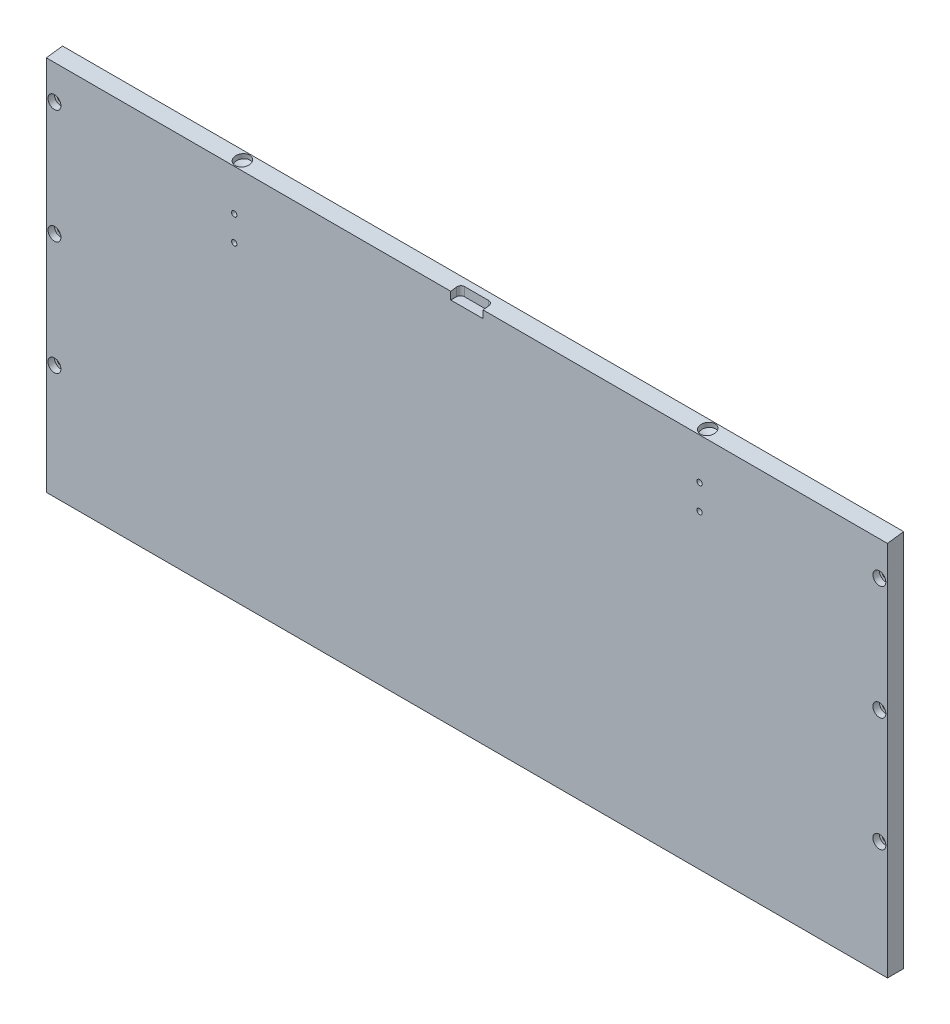
SolidWorks part; units mm, degrees
material "Bakelite Black"
ref_plane "Front" through (0, 0, 0) normal (0, 0, 1) x (1, 0, 0)
ref_plane "Top" through (0, 0, 0) normal (0, 1, 0) x (1, 0, 0)
ref_plane "Right" through (0, 0, 0) normal (1, 0, 0) x (0, 0, -1)
sketch "Sketch1" plane through (0, 0, 0) normal (0, 0, 1) x (1, 0, 0)
  line L1 (0, 0) -> (520, 0)
  line L2 (0, 0) -> (0, 234)
  line L3 (0, 234) -> (520, 234)
  line L4 (520, 0) -> (520, 234)
  dimension "D1" = 234
  dimension "D2" = 520
extrude "Boss-Extrude1" add sketch "Sketch1" along normal blind 10
ref_plane "Plane1" through (260, 0, 0) normal (-1, 0, 0) x (0, 0, 1)
sketch "Sketch8" plane through (0, 0, 10) normal (0, 0, 1) x (1, 0, 0)
  line L0 (260, 5.5) -> (260, -5.5) construction
  line L1 (250, 228) -> (270, 228)
  line L2 (250, 228) -> (250, 236)
  line L3 (250, 236) -> (270, 236)
  line L4 (270, 228) -> (270, 236)
  line L5 (250, 228) -> (270, 236) construction
  line L6 (250, 236) -> (270, 228) construction
  line L7 (520, 234) -> (0, 234) construction
  point P0 (260, 232)
  dimension "D1" = 20
  dimension "D2" = 8
  dimension "D3" = 6
extrude "Cut-Extrude5" cut sketch "Sketch8" against normal blind 6
fillet "Fillet2" radius 2.5 2 edges at (270, 231, 4) (250, 231, 4)
sketch "Sketch9" plane through (0, 0, 0) normal (1, 0, 0) x (0, 0, -1)
  line L0 (0, 234) -> (-10, 232.6853)
  line L1 (-10, 234) -> (-10, 0) construction
  line L2 (-10, 232.6853) -> (-10, 234)
  line L3 (-10, 234) -> (0, 234)
  dimension "D1" = 7.49
extrude "Cut-Extrude7" cut sketch "Sketch9" along normal through all
hole_wizard "M4x0.7 Tapped Hole1" positions "Sketch10" profile "Sketch11" tap size "M4x0.7" standard "ANSI Metric"
sketch "Sketch10" plane through (0, 0, 0) normal (0, -1, 0) x (-1, 0, 0)
  line L0 (-260, -8.8296) -> (-260, 8.8296) construction
  line L1 (0, 0) -> (-520, 0) construction
  point P0 (-70, -5)
  point P2 (-260, -5)
  point P4 (-450, -5)
  dimension "D1" = 190
  dimension "D2" = 190
  dimension "D3" = 5
sketch "Sketch11" plane through (70, 0, 5) normal (1, 0, 0) x (0, 0, -1)
  line L0 (0, 0) -> (0, 12.9914)
  line L1 (0, 12.9914) -> (1.65, 12)
  line L2 (1.65, 12) -> (1.65, 0)
  line L5 (1.65, 0) -> (0, 0)
  line L10 (0, 12.9914) -> (-1.65, 12) construction
  line L11 (0, -6.35) -> (0, 107.95) construction
  dimension "Tap Drill Dia." = 3.3
  dimension "Tap Drill Depth" = 12
  dimension "Drill Angle" = 118
cosmetic thread "Hole Thread1" parameters "D1"=8, "D2"=4
cosmetic thread "Hole Thread2" parameters "D1"=8, "D2"=4
cosmetic thread "Hole Thread3" parameters "D1"=8, "D2"=4
hole_wizard "CBORE for M4 SHCS1" positions "Sketch12" profile "Sketch13" counterbore size "M4" standard "ANSI Metric"
sketch "Sketch12" plane through (0, 0, 10) normal (0, 0, 1) x (1, 0, 0)
  line L0 (0, 0) -> (520, 0) construction
  line L1 (0, 232.6853) -> (0, 0) construction
  point P0 (5, 211.5)
  point P2 (5, 141)
  point P4 (5, 70.5)
  dimension "D1" = 70.5
  dimension "D2" = 70.5
  dimension "D3" = 70.5
  dimension "D4" = 5
sketch "Sketch13" plane through (5, 211.5, 10) normal (1, 0, 0) x (0, -1, 0)
  line L0 (0, 0) -> (0, 13.3519)
  line L1 (0, 13.3519) -> (2.25, 12)
  line L2 (2.25, 12) -> (2.25, 4)
  line L3 (2.25, 4) -> (4, 4)
  line L4 (4, 4) -> (4, 0)
  line L5 (4, 0) -> (0, 0)
  line L10 (0, 13.3519) -> (-2.25, 12) construction
  line L11 (0, -6.35) -> (0, 107.95) construction
  dimension "Hole Dia." = 4.5
  dimension "Hole Depth" = 12
  dimension "C'Bore Dia." = 8
  dimension "C'Bore Depth" = 4
  dimension "Drill Angle" = 118
mirror "Mirror1" about plane through (260, 0, 0) normal (-1, 0, 0) of "CBORE for M4 SHCS1"
hole_wizard "M4x0.7 Tapped Hole2" positions "Sketch14" profile "Sketch15" tap size "M4x0.7" standard "ANSI Metric" end condition through all
sketch "Sketch14" plane through (0, 0, 10) normal (0, 0, 1) x (1, 0, 0)
  line L0 (250, 232.6853) -> (0, 232.6853) construction
  line L1 (260, 8.8296) -> (260, -8.8296) construction
  point P0 (116.15, 207.1853)
  point P2 (116.15, 191.6853)
  dimension "D1" = 15.5
  dimension "D2" = 25.5
  dimension "D3" = 143.85
sketch "Sketch15" plane through (116.15, 207.1853, 10) normal (1, 0, 0) x (0, -1, 0)
  line L0 (0, 0) -> (0, 10)
  line L1 (0, 10) -> (1.65, 10)
  line L2 (1.65, 10) -> (1.65, 0)
  line L5 (1.65, 0) -> (0, 0)
  line L11 (0, -6.35) -> (0, 107.95) construction
  dimension "Thru Tap Drill Dia." = 3.3
  dimension "Thru Tap Drill Depth" = 10
cosmetic thread "Hole Thread4" parameters "D2"=4
cosmetic thread "Hole Thread5" parameters "D2"=4
mirror "Mirror2" about plane through (260, 0, 0) normal (-1, 0, 0) of "M4x0.7 Tapped Hole2"
hole_wizard "Ø9.0 (9) Diameter Hole1" positions "Sketch16" profile "Sketch17" hole size "Ø9.0" standard "ANSI Metric"
sketch "Sketch16" plane through (0, 230.0239, 30.2424) normal (0, 0.9915, 0.1304) x (1, 0, 0)
  line L0 (260, 8.8296) -> (260, -8.8296) construction
  line L1 (520, 30.5026) -> (0, 30.5026) construction
  point P0 (116.15, 25.5026)
  dimension "D1" = 143.85
  dimension "D2" = 5
sketch "Sketch17" plane through (116.15, 233.3482, 4.9573) normal (1, 0, 0) x (0, -0.1304, 0.9915)
  line L0 (0, 0) -> (0, 5.7039)
  line L1 (0, 5.7039) -> (4.5, 3)
  line L2 (4.5, 3) -> (4.5, 0)
  line L5 (4.5, 0) -> (0, 0)
  line L10 (0, 5.7039) -> (-4.5, 3) construction
  line L11 (0, -6.35) -> (0, 107.95) construction
  dimension "Hole Dia." = 9
  dimension "Hole Depth" = 3
  dimension "Drill Angle" = 118
mirror "Mirror5" about plane through (260, 0, 0) normal (-1, 0, 0) of "Ø9.0 (9) Diameter Hole1"
